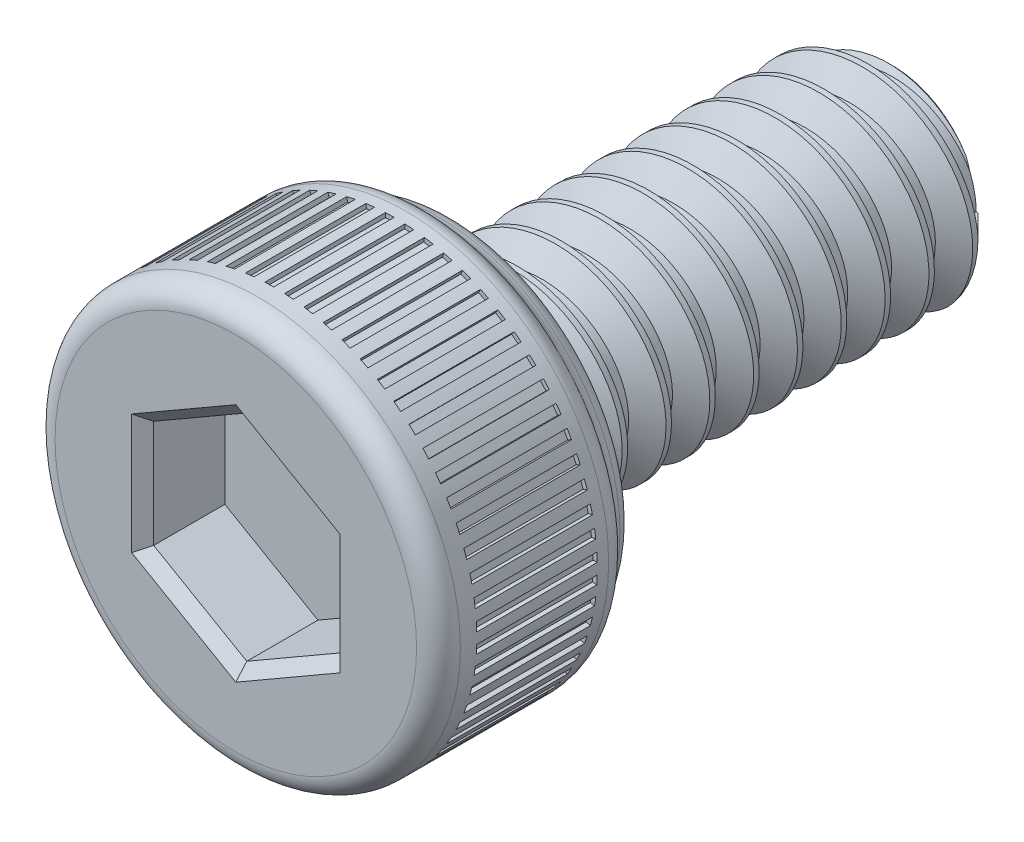
SolidWorks part; units mm, degrees
material "Alloy Steel"
ref_plane "Front Plane" through (0, 0, 0) normal (1, 0, 0) x (0, 1, 0)
ref_plane "Top Plane" through (0, 0, 0) normal (0, 0, 1) x (0, 1, 0)
ref_plane "Right Plane" through (0, 0, 0) normal (0, 1, 0) x (-1, 0, 0)
ref_axis "x axis" through (-88.99, 0, 0) along (1, 0, 0)
ref_axis "y xxis" through (0, 88.99, 0) along (0, -1, 0)
ref_axis "z axis" through (0, 0, 55) along (0, 0, -1)
sketch "Sketch2" plane through (0, 0, 0) normal (1, 0, 0) x (0, 1, 0)
  line L0 (0, 0) -> (1.85, 0)
  line L1 (1.85, 0) -> (1.85, -1.7)
  line L3 (0.975, -2) -> (0.975, -5.8)
  line L5 (0, -5.8) -> (0, 0)
  line L6 (0.975, -5.8) -> (0.775, -6)
  line L7 (0.775, -6) -> (0, -6)
  line L8 (0, -6) -> (0, -5.8)
  line L9 (0, -5.8) -> (0.975, -5.8) construction
  line L10 (0.975, -2) -> (1.65, -2)
  line L11 (1.65, -2) -> (1.65, -1.7)
  line L12 (1.65, -1.7) -> (1.85, -1.7)
  point P3 (1.95, -1.0694)
  dimension "D1" = 0.975
  dimension "D2" = 2
  dimension "D3" = 4
  dimension "D4" = 1.85
  dimension "D5" = 45
  dimension "D6" = 0.2
  dimension "D7" = 0.3
  dimension "D8" = 1.65
revolve "Revolve1" add sketch "Sketch2" angle 360 about L5
sketch "Sketch3" plane through (0, 0, 0) normal (0, 0, 1) x (1, 0, 0)
  line L1 (0.85, 0.4907) -> (0, 0.9815)
  line L2 (0, 0.9815) -> (-0.85, 0.4907)
  line L3 (-0.85, 0.4907) -> (-0.85, -0.4907)
  line L4 (-0.85, -0.4907) -> (0, -0.9815)
  line L5 (0, -0.9815) -> (0.85, -0.4907)
  line L6 (0.85, -0.4907) -> (0.85, 0.4907)
  circle A0 centre (0, 0) radius 0.85 construction
  dimension "D1" = 1.7
extrude "Cut-Extrude1" cut sketch "Sketch3" against normal blind 0.75
thread "Thread1" pitch 0.4 method cut profile "Thread Profile1" start angle 0, offset 0, length 0, pitch 0.4, diameter 1.95
ref_plane "Plane1" through (-0.975, 0, -2) normal (0, -1, 0) x (-1, 0, 0)
sketch "Thread Profile1" plane through (-0.975, 0, -2) normal (0, -1, 0) x (-1, 0, 0)
  line L0 (0, 0) -> (0, 0.4) construction
  line L11 (0, 0) -> (0, 0.35)
  line L12 (0, 0.35) -> (-0.2165, 0.225)
  line L13 (-0.2165, 0.225) -> (-0.2165, 0.125)
  line L15 (-0.2165, 0.125) -> (0, 0)
  line L17 (-0.2165, 0.175) -> (0, 0.175) construction
  point P2 (0, 0)
  dimension "Pitch" = 0.4
  dimension "Profile_Angle" = 60
  dimension "Profile_Land" = 0.1
  dimension "Profile_Height" = 0.2165
fillet "Fillet1" radius 0.2 2 edges at (-1.65, 0, -1.7) (-1.85, 0, 0)
chamfer "Chamfer1" distance 0.1 angle 45 6 edges at (-0.425, 0.7361, 0) (-0.85, 0, 0) (0.425, 0.7361, 0) (0.85, 0, 0) (0.425, -0.7361, 0) (-0.425, -0.7361, 0)
fillet "Fillet2" radius 0.2 2 edges at (-1.65, 0, -2) (-1.85, 0, -1.7)
ref_plane "Plane2" through (0, 0, -0.2) normal (0, 0, 1) x (0, -1, 0)
ref_plane "Plane3" through (0, 0, -0.35) normal (0, 0, 1) x (0, -1, 0)
sketch "Sketch6" plane through (0, 0, -0.35) normal (0, 0, 1) x (0, -1, 0)
  line L0 (0, -1.81) -> (0, 0) construction
  line L1 (-0.04, -1.8798) -> (0.04, -1.8798)
  line L2 (-0.04, -1.8798) -> (-0.04, -1.81)
  line L3 (-0.04, -1.81) -> (0.04, -1.81)
  line L4 (0.04, -1.8798) -> (0.04, -1.81)
  dimension "D1" = 1.81
  dimension "D2" = 0.08
extrude "Cut-Extrude2" cut sketch "Sketch6" against normal blind 1.1
ref_axis "Axis1" through (0, 0, 0) along (0, 0, 1)
pattern_circular "CirPattern1" count 65 over 360 about axis through (0, 0, 0) along (0, 0, 1) of "Cut-Extrude2"
